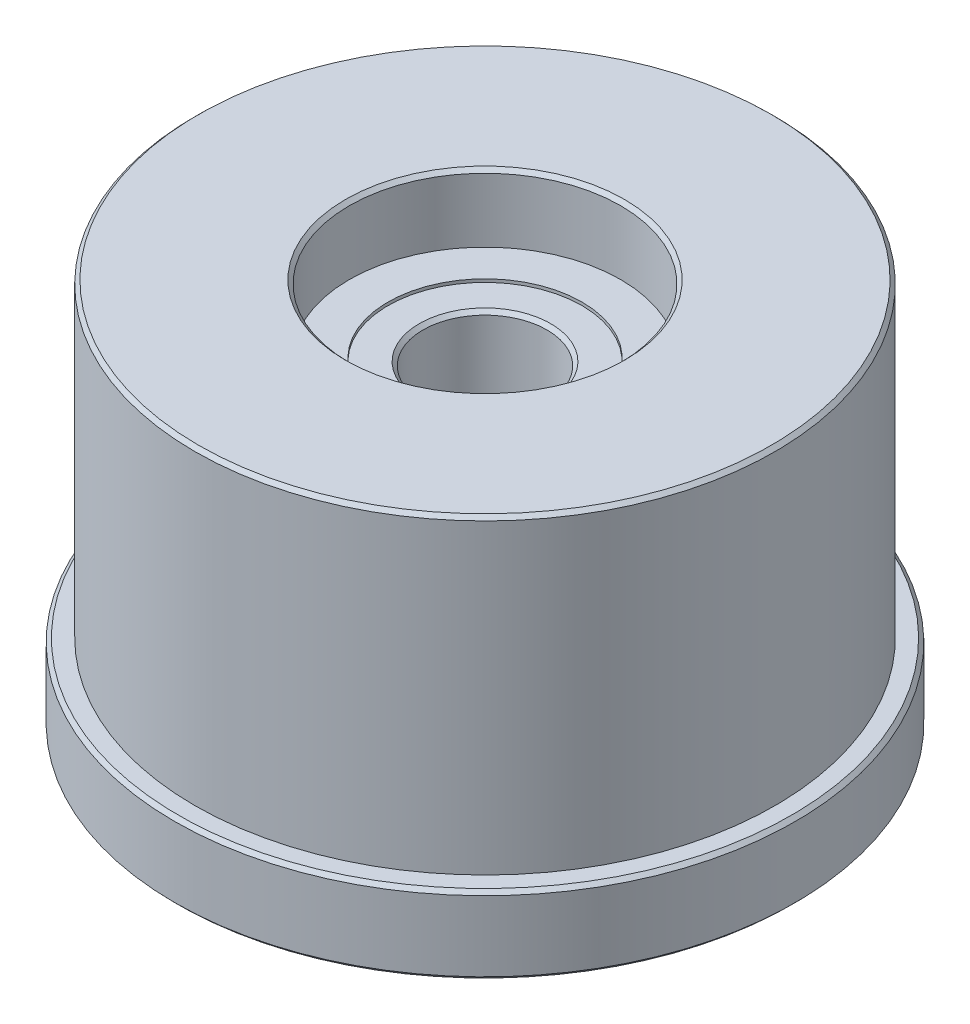
SolidWorks part; units mm, degrees
material "Nylon 101"
ref_plane "Front Plane" through (0, 0, 0) normal (0, 0, 1) x (1, 0, 0)
ref_plane "Top Plane" through (0, 0, 0) normal (0, 1, 0) x (1, 0, 0)
ref_plane "Right Plane" through (0, 0, 0) normal (1, 0, 0) x (0, 0, -1)
sketch "Sketch1" plane through (0, 0, 0) normal (0, 1, 0) x (1, 0, 0)
  circle A0 centre (0, 0) radius 23.749
  dimension "D1" = 47.498
extrude "Boss-Extrude1" add sketch "Sketch1" along normal blind 25.4
sketch "Sketch2" plane through (0, 0, 0) normal (0, -1, 0) x (1, 0, 0)
  circle A0 centre (0, 0) radius 25.4
  dimension "D1" = 50.8
extrude "Boss-Extrude2" add sketch "Sketch2" along normal blind 6.35
sketch "Sketch3" plane through (0, -6.35, 0) normal (0, -1, 0) x (1, 0, 0)
  circle A0 centre (0, 0) radius 5.08
  dimension "D1" = 10.16
extrude "Cut-Extrude1" cut sketch "Sketch3" against normal through all
sketch "Sketch4" plane through (0, -6.35, 0) normal (0, -1, 0) x (1, 0, 0)
  circle A0 centre (0, 0) radius 11.1125
  dimension "D1" = 22.225
extrude "Cut-Extrude2" cut sketch "Sketch4" against normal blind 5.5372
sketch "Sketch5" plane through (0, -0.8128, 0) normal (0, -1, 0) x (1, 0, 0)
  circle A0 centre (0, 0) radius 7.9375
  dimension "D1" = 15.875
extrude "Cut-Extrude3" cut sketch "Sketch5" against normal blind 0.254
ref_plane "Plane1" through (0, 9.525, 0) normal (0, 1, 0) x (1, 0, 0)
mirror "Mirror1" about plane through (0, 9.525, 0) normal (0, 1, 0) of "Cut-Extrude2", "Cut-Extrude3"
chamfer "Chamfer1" distance 0.3 angle 45 7 edges at (0, 0, -25.4) (0, -6.35, -25.4) (0, -6.35, -11.1125) (0, 25.4, 23.749) (0, 19.6088, 5.08) (0, -0.5588, -5.08) (0, 25.4, -11.1125)
equation "\"D1@Chamfer1\"=.3mm"
